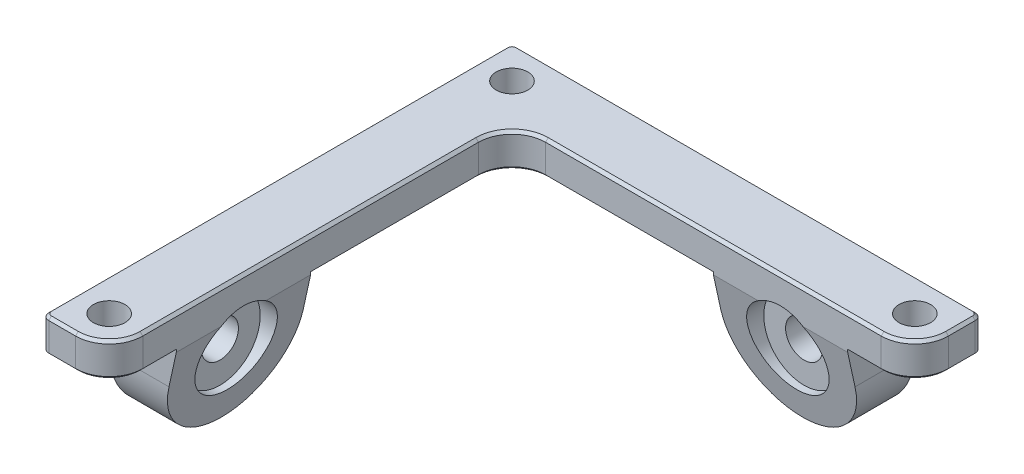
SolidWorks part; units mm, degrees
material "ABS"
ref_plane "Front Plane" through (0, 0, 0) normal (0, 0, 1) x (1, 0, 0)
ref_plane "Top Plane" through (0, 0, 0) normal (0, 1, 0) x (1, 0, 0)
ref_plane "Right Plane" through (0, 0, 0) normal (1, 0, 0) x (0, 0, -1)
sketch "Sketch1" plane through (0, 0, 0) normal (0, 1, 0) x (1, 0, 0)
  line L0 (-35, 35) -> (-35, -35)
  line L1 (-30, -30) -> (30, -30) construction
  line L2 (-30, -30) -> (-30, 30) construction
  line L3 (-30, 30) -> (30, 30) construction
  line L4 (30, -30) -> (30, 30) construction
  line L5 (-30, -30) -> (30, 30) construction
  line L6 (-30, 30) -> (30, -30) construction
  line L11 (-35, -35) -> (-30, -35)
  line L12 (-25, -30) -> (-25, 20)
  line L13 (-20, 25) -> (30, 25)
  line L14 (-35, 35) -> (35, 35)
  line L15 (35, 35) -> (35, 30)
  circle A0 centre (-30, -30) radius 2.35
  circle A1 centre (-30, 30) radius 2.35
  circle A2 centre (30, 30) radius 2.35
  circle A3 centre (30, -30) radius 2.35 construction
  circle A4 centre (-30, 30) radius 5 construction
  arc A6 (-25, -30) -> (-30, -35) centre (-30, -30) ccw construction
  arc A7 (35, 30) -> (30, 25) centre (30, 30) ccw construction
  arc A8 (-25, 20) -> (-20, 25) centre (-20, 20) cw
  arc A9 (-30, -35) -> (-25, -30) centre (-30, -30) ccw
  arc A10 (30, 25) -> (35, 30) centre (30, 30) ccw
  point P0 (0, 0)
  dimension "D3" = 4.7
  dimension "D4" = 5
  dimension "D1" = 60
  dimension "D2" = 60
extrude "Boss-Extrude1" add sketch "Sketch1" along normal blind 5
sketch "Sketch2" plane through (-35, 0, 0) normal (-1, 0, 0) x (0, 0, 1)
  line L0 (-35, 5) -> (35, 5) construction
  line L1 (5, 5) -> (25, 5)
  line L2 (5, 5) -> (5, -15)
  line L3 (5, -15) -> (25, -15)
  line L4 (25, 5) -> (25, -15)
  line L5 (15, -5) -> (5, -5) construction
  line L7 (15, -5) -> (25, -5) construction
  line L8 (35, 5) -> (35, 0) construction
  circle A0 centre (15, -5) radius 2.75
  dimension "D3" = 5.5
  dimension "D1" = 20
  dimension "D2" = 20
  dimension "D5" = 10
extrude "Boss-Extrude2" add sketch "Sketch2" against normal blind 6.5
fillet "Fillet1" radius 10 2 edges at (-31.75, -15, 5) (-31.75, -15, 25)
sketch "Sketch3" plane through (-28.5, 0, 0) normal (1, 0, 0) x (0, 0, -1)
  circle A0 centre (-15, -5) radius 6
  dimension "D1" = 12
chamfer "Chamfer1" distance 3.5 distance2 16 1 edges at (-28.5, 0, 15)
extrude "Cut-Extrude2" cut sketch "Sketch3" along normal through all
ref_plane "Plane1" through (0, 0, 0) normal (-0.7071, 0, 0.7071) x (0.7071, 0, 0.7071)
split "Split1" trim tools "Plane1" bodies to split 104 resulting bodies 105 106
delete or keep bodies "Body-Delete/Keep 1" type delete bodies bodies 106
mirror "Mirror3" about plane through (0, 0, 0) normal (-0.7071, 0, 0.7071) of bodies 105
fillet "Fillet2" radius 1 3 edges at (35, 2.5, -35) (-35, 2.5, -35) (-35, 2.5, 35)
chamfer "Chamfer2" distance 0.4 angle 45 28 edges at (-23.5355, 0, -23.5355) (-25, 0, 27.5) (-26.4645, 0, 33.5355) (29.5, 0, -35) (33.5355, 0, -26.4645) (27.5, 0, -25) (-7.5, 0, -25) (33.5355, 5, -26.4645) (5, 5, -25) (-26.4645, 5, 33.5355) (-14.5, 0, -35) (0, 5, -35) (35, 0, -32) (34.7071, 0, -34.7071) (35, 5, -32) (-35, 5, 0) (-32, 5, 35) (-34.7071, 5, 34.7071) (-34.7071, 5, -34.7071) (34.7071, 5, -34.7071) (-35, 0, -14.5) (-34.7071, 0, -34.7071) (-32, 0, 35) (-34.7071, 0, 34.7071) (-25, 5, 5) (-23.5355, 5, -23.5355) (-35, 0, 29.5) (-25, 0, -7.5)
